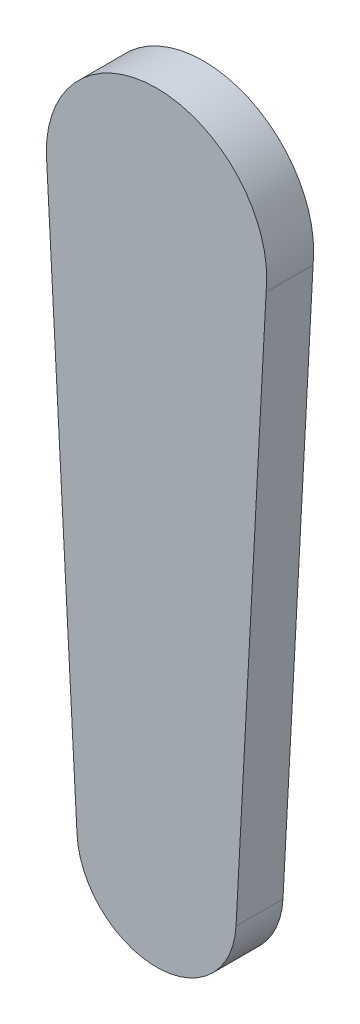
SolidWorks part; units mm, degrees
ref_plane "前视基准面" through (0, 0, 0) normal (0, 0, 1) x (1, 0, 0)
ref_plane "上视基准面" through (0, 0, 0) normal (0, 1, 0) x (1, 0, 0)
ref_plane "右视基准面" through (0, 0, 0) normal (1, 0, 0) x (0, 0, -1)
sketch "草图1" plane through (0, 0, 0) normal (0, 0, 1) x (1, 0, 0)
  line L0 (0, -70) -> (0, 70)
  line L1 (-27, 70) -> (-19.4723, -71.0393)
  line L2 (27, 70) -> (19.4723, -71.0393)
  circle A0 centre (0, 70) radius 27
  circle A1 centre (0, -70) radius 19.5
  point P4 (0, 0)
  dimension "D2" = 54
  dimension "D3" = 39
  dimension "D1" = 140
extrude "凸台-拉伸1" add sketch "草图1" along normal blind 11.5 contours A0
extrude "凸台-拉伸2" add sketch "草图1<5>" along normal blind 11.5 contours A1 L2 A0 L0 | A1 L0 A0 L1 | A1 region at (-12.2305, -1.2051, 0) region at (12.2305, -1.2051, 0)
sketch "草图1<5>" plane through (0, 0, 0) normal (0, 0, 1) x (1, 0, 0) same geometry as "草图1"
